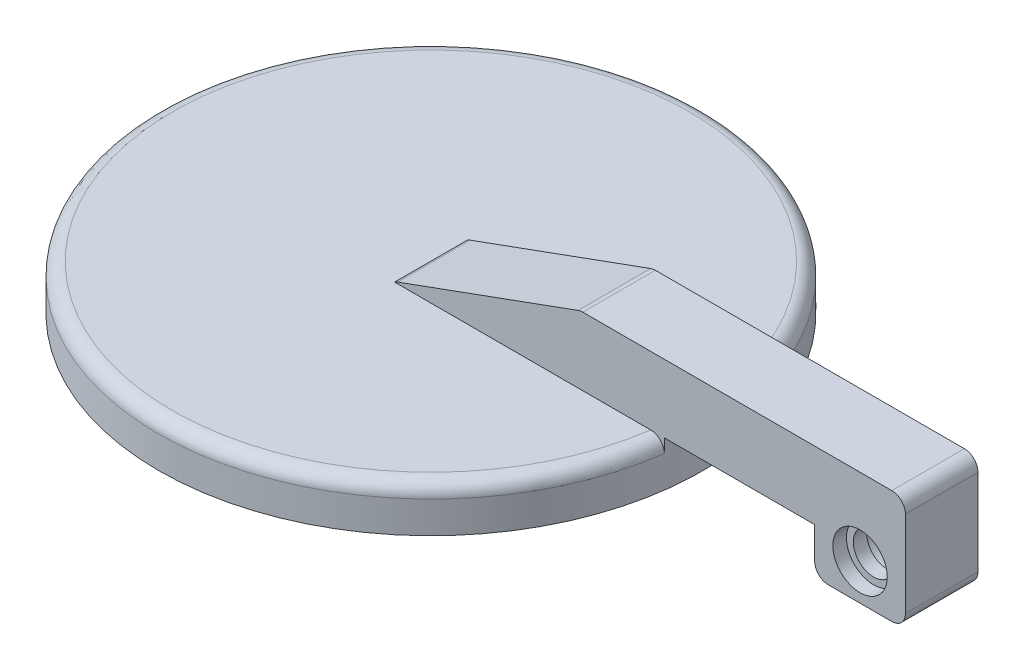
SolidWorks part; units mm, degrees
ref_plane "Front Plane" through (0, 0, 0) normal (0, 0, 1) x (1, 0, 0)
ref_plane "Top Plane" through (0, 0, 0) normal (0, 1, 0) x (1, 0, 0)
ref_plane "Right Plane" through (0, 0, 0) normal (1, 0, 0) x (0, 0, -1)
sketch "Sketch2" plane through (0, 0, 0) normal (0, 0, 1) x (1, 0, 0)
  line L7 (0, 0) -> (30, 0)
  line L8 (0, 0) -> (0, 5)
  line L9 (0, 5) -> (30, 5)
  line L10 (30, 0) -> (30, 5)
  dimension "D1" = 5
  dimension "D2" = 30
revolve "Revolve1" add sketch "Sketch2" angle 360 about L8
sketch "Sketch3" plane through (0, 5, 0) normal (0, 1, 0) x (1, 0, 0)
  line L0 (0, -10) -> (0, 10) construction
  line L1 (0, 10) -> (35, 10)
  line L2 (35, 10) -> (35, 6)
  line L3 (35, 6) -> (0, 6)
  line L4 (0, 10) -> (0, 6)
  line L5 (0, -10) -> (35, -10)
  line L6 (35, -10) -> (35, -6)
  line L7 (35, -6) -> (0, -6)
  line L8 (0, -6) -> (0, -10)
  line L9 (0, 4) -> (0, -4)
  line L10 (0, 4) -> (56.3, 4)
  line L11 (0, -4) -> (56.3, -4)
  line L12 (56.3, -4) -> (56.3, 4)
  point P4 (0, 0)
  point P13 (0, 0)
  circle M1 centre (0, 0) radius 30
  dimension "D1" = 20
  dimension "D2" = 35
  dimension "D3" = 4
  dimension "0.7" = 8
  dimension "D5" = 56.3
extrude "Boss-Extrude1" add sketch "Sketch3" along normal blind 7.5 contours L9 L11 L10 M1 | L11 L12 L10 M1 region at (14.9555, 5, 0) region at (43.1053, 5, 0)
sketch "Sketch4" plane through (0, 0, 0) normal (0, 0, 1) x (1, 0, 0)
  line L5 (35, 8.75) -> (37.8, 8.75) construction
  line L7 (56.3, 8.75) -> (37.8, 8.75) construction
  line L8 (56.3, 12.5) -> (56.3, 5) construction
  line L10 (-0.1339, 5) -> (20.4721, 12.5)
  line L11 (29.7321, 5) -> (-30, 5) construction
  line L12 (0, 12.5) -> (56.3, 12.5) construction
  line L13 (0, 5) -> (29.7321, 5) construction
  line L14 (20.4721, 12.5) -> (0, 12.5)
  line L15 (0, 12.5) -> (-0.1339, 5)
  circle A0 centre (37.8, 8.75) radius 2
  dimension "D3" = 4
  dimension "D1" = 20
  dimension "D2" = 18.5
extrude "Cut-Extrude1" cut sketch "Sketch4" against normal mid plane 30 contours L14 L15 L10
sketch "Sketch6" plane through (0, 5, 0) normal (0, -1, 0) x (1, 0, 0)
  line L6 (56.3, 4) -> (46.3, 4)
  line L7 (56.3, 4) -> (56.3, -4) construction
  line L8 (29.7321, 4) -> (56.3, 4) construction
  line L9 (46.3, 4) -> (46.3, -4)
  line L10 (29.7321, -4) -> (56.3, -4) construction
  line L11 (46.3, -4) -> (56.3, -4)
  line L12 (56.3, -4) -> (56.3, 4)
  dimension "D1" = 10
extrude "Boss-Extrude2" add sketch "Sketch6" along normal blind 5
sketch "Sketch7" plane through (0, 0, 4) normal (0, 0, 1) x (1, 0, 0)
  line L0 (51.3, 4) -> (51.3, 0) construction
  line L2 (56.3, 0) -> (46.3, 0) construction
  circle A0 centre (51.3, 4) radius 3
  dimension "D2" = 6
  dimension "D1" = 4
extrude "Cut-Extrude2" cut sketch "Sketch7" against normal blind 10
fillet "Fillet2" radius 1.5 6 edges at (46.3, 0, 0) (56.3, 0, 0) (56.3, 12.5, 0) (20.4721, 12.5, 0) (0, 5.0487, 0) (-30, 5, 0)
sketch "Sketch9" plane through (0, 0, -4) normal (0, 0, -1) x (-1, 0, 0)
  circle A0 centre (-51.3, 4) radius 3
  circle A1 centre (-51.3, 4) radius 4
  dimension "D1" = 6
  dimension "D2" = 8
sketch "Sketch10" plane through (0, 0, 4) normal (0, 0, 1) x (1, 0, 0)
  circle A0 centre (51.3, 4) radius 3.25
  circle A1 centre (51.3, 4) radius 2.25
  dimension "D1" = 6.5
  dimension "D2" = 4.5
extrude "Boss-Extrude4" add sketch "Sketch10" along normal blind 1.5 from offset 3 offset against normal yes
sketch "Sketch11" plane through (0, 0, 1) normal (0, 0, -1) x (-1, 0, 0)
  circle A0 centre (-51.3, 4) radius 2.6
  circle A1 centre (-51.3, 4) radius 3
  dimension "D1" = 5.2
  dimension "D2" = 6
sketch "Sketch12" plane through (0, 0, 0) normal (0, -1, 0) x (1, 0, 0)
  line L0 (0, 30) -> (0, 25.5) construction
  circle A0 centre (0, 0) radius 30 construction
  circle A1 centre (0, 27.75) radius 1.5
  circle A2 centre (19.6222, 19.6222) radius 1.5
  circle A3 centre (27.75, 0) radius 1.5
  circle A4 centre (19.6222, -19.6222) radius 1.5
  circle A5 centre (0, -27.75) radius 1.5
  circle A6 centre (-19.6222, -19.6222) radius 1.5
  circle A7 centre (-27.75, 0) radius 1.5
  circle A8 centre (-19.6222, 19.6222) radius 1.5
  point P24 (0, 0)
  dimension "D2" = 3
  dimension "D1" = 4.5
  dimension "D3" = 8
extrude "Cut-Extrude3" cut sketch "Sketch12" against normal blind 0.5
